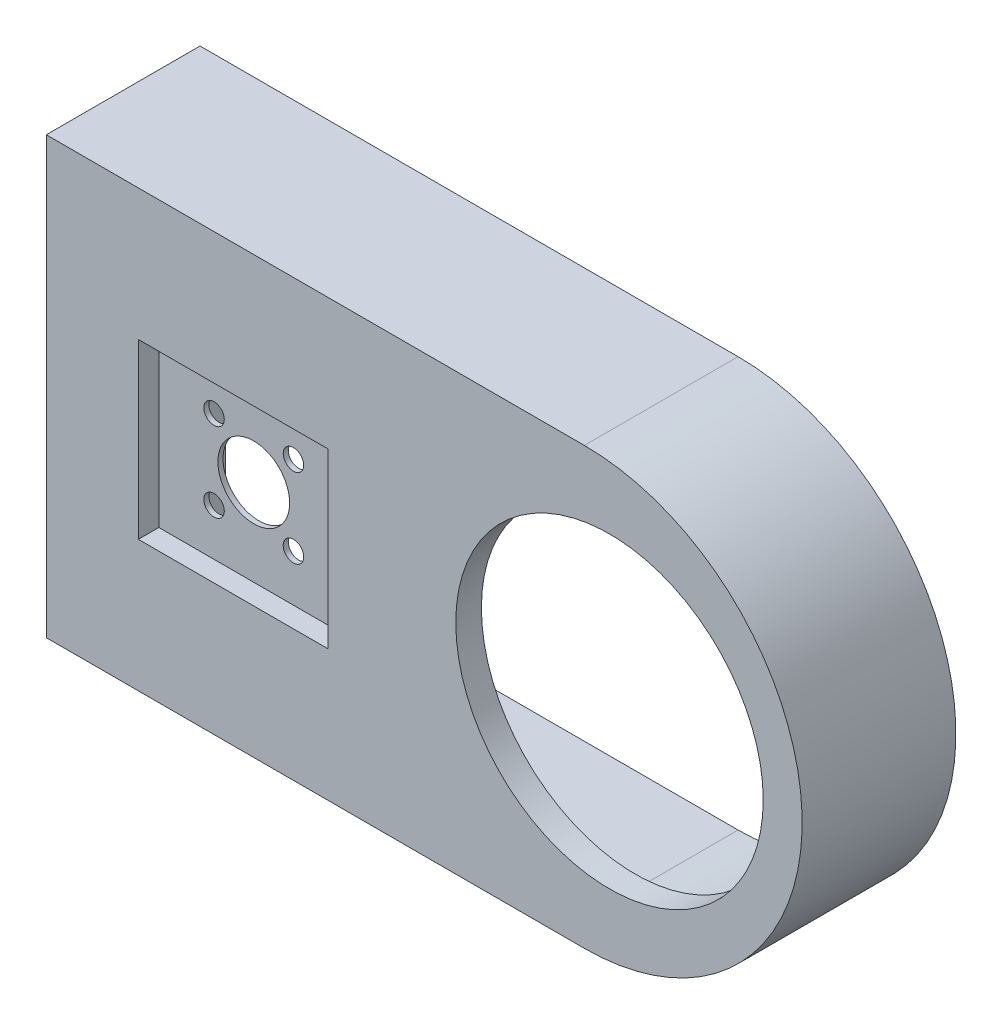
SolidWorks part; units mm, degrees
ref_plane "Front Plane" through (0, 0, 0) normal (0, 0, 1) x (1, 0, 0)
ref_plane "Top Plane" through (0, 0, 0) normal (0, 1, 0) x (1, 0, 0)
ref_plane "Right Plane" through (0, 0, 0) normal (1, 0, 0) x (0, 0, -1)
sketch "Sketch1" plane through (0, 0, 0) normal (0, 0, 1) x (1, 0, 0)
  line L1 (-100, -75) -> (100, -75)
  line L2 (-100, -75) -> (-100, 75)
  line L3 (-100, 75) -> (100, 75)
  line L5 (-100, -75) -> (100, 75) construction
  line L6 (-100, 75) -> (100, -75) construction
  arc A0 (100, -75) -> (100, 75) centre (100, 0) ccw
  point P0 (0, 0)
  point P7 (-270.7912, 47.9946)
  dimension "D1" = 150
  dimension "D2" = 200
extrude "Extrude-Thin1" add sketch "Sketch1" against normal blind 60 thin thin type one direction wall 10
extrude "Boss-Extrude1" add sketch "Sketch1<2>" against normal blind 10
sketch "Sketch1<2>" plane through (0, 0, 0) normal (0, 0, 1) x (1, 0, 0) same geometry as "Sketch1"
sketch "Sketch2" plane through (0, 0, -10) normal (0, 0, -1) x (-1, 0, 0)
  line L0 (87.1431, 0) -> (-146.9195, 0) construction
  circle A0 centre (-109.812, 0) radius 60
  circle A1 centre (22.4429, 0) radius 11.3481
  dimension "D1" = 120
extrude "Cut-Extrude1" cut sketch "Sketch2" against normal through all contours A0 region at (109.812, 0, -10)
sketch "Sketch3" plane through (0, 0, 0) normal (0, 0, 1) x (1, 0, 0)
  line L1 (-74.0642, -33.7773) -> (0, -33.7773)
  line L2 (-74.0642, -33.7773) -> (-74.0642, 33.7773)
  line L3 (-74.0642, 33.7773) -> (0, 33.7773)
  line L4 (0, -33.7773) -> (0, 33.7773)
  line L5 (-74.0642, -33.7773) -> (0, 33.7773) construction
  line L6 (-74.0642, 33.7773) -> (0, -33.7773) construction
  circle A0 centre (-37.0321, 0) radius 14
  point P0 (-37.0321, 0)
  dimension "D1" = 28
extrude "Cut-Extrude2" cut sketch "Sketch3" against normal blind 8
extrude "Cut-Extrude3" cut sketch "Sketch3<2>" against normal through all contours A0 region at (-37.0321, 0, 0)
sketch "Sketch3<2>" plane through (0, 0, 0) normal (0, 0, 1) x (1, 0, 0) same geometry as "Sketch3"
sketch "Sketch7" plane through (0, 0, -8) normal (0, 0, 1) x (1, 0, 0)
  line L0 (-37.0321, 0) -> (29.0023, 51.6136) construction
  line L1 (-37.0321, 23.8285) -> (-37.0321, -31.7952) construction
  line L2 (-4.3524, 0) -> (-68.8791, 0) construction
  circle A0 centre (-52.5321, 15.5) radius 4
  circle A2 centre (-21.5321, 15.5) radius 4
  circle A3 centre (-21.5321, -15.5) radius 4
  circle A4 centre (-52.5321, -15.5) radius 4
  dimension "D1" = 8
  dimension "D2" = 15.5
  dimension "D3" = 15.5
extrude "Cut-Extrude4" cut sketch "Sketch7" against normal through all
